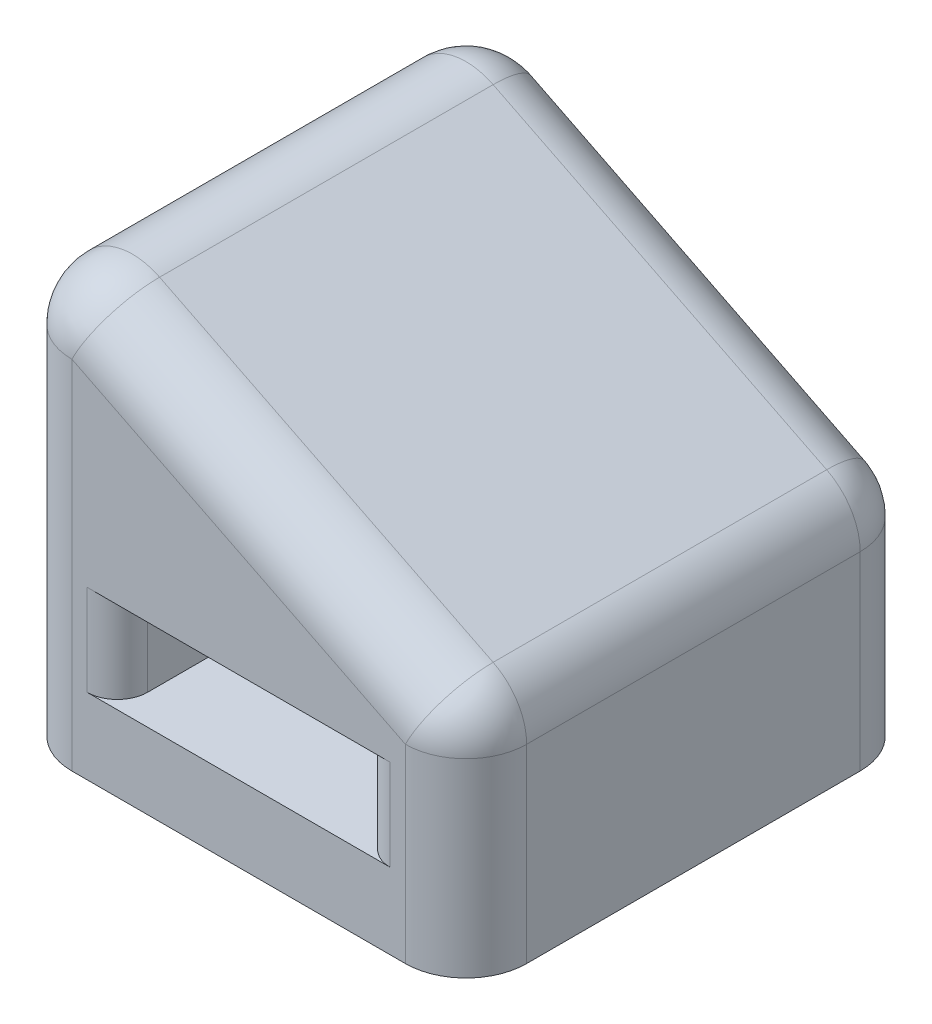
SolidWorks part; units mm, degrees
ref_plane "Plano frontal" through (0, 0, 0) normal (0, 0, 1) x (1, 0, 0)
ref_plane "Plano superior" through (0, 0, 0) normal (0, 1, 0) x (1, 0, 0)
ref_plane "Plano direito" through (0, 0, 0) normal (1, 0, 0) x (0, 0, -1)
sketch "Esboço1" plane through (0, 0, 0) normal (0, 1, 0) x (1, 0, 0)
  line L1 (-5.5, -7.5) -> (5.5, -7.5)
  line L2 (-7.5, -5.5) -> (-7.5, 5.5)
  line L3 (-5.5, 7.5) -> (5.5, 7.5)
  line L4 (7.5, -5.5) -> (7.5, 5.5)
  line L5 (-7.5, -7.5) -> (7.5, 7.5) construction
  line L6 (-7.5, 7.5) -> (7.5, -7.5) construction
  arc A0 (7.5, 5.5) -> (5.5, 7.5) centre (5.5, 5.5) ccw
  arc A1 (7.5, -5.5) -> (5.5, -7.5) centre (5.5, -5.5) cw
  arc A2 (-5.5, -7.5) -> (-7.5, -5.5) centre (-5.5, -5.5) cw
  arc A3 (-7.5, 5.5) -> (-5.5, 7.5) centre (-5.5, 5.5) cw
  point P0 (0, 0)
  dimension "D3" = 2
  dimension "D1" = 15
  dimension "D2" = 15
extrude "Ressalto-extrusão1" add sketch "Esboço1" along normal blind 15
sketch "Esboço2" plane through (0, 0, 7.5) normal (0, 0, 1) x (1, 0, 0)
  line L0 (-7.5, 15) -> (7.5, 7.5)
  line L1 (7.5, 15) -> (7.5, 0) construction
  line L2 (7.5, 7.5) -> (7.5, 15)
  line L3 (7.5, 15) -> (-7.5, 15)
extrude "Corte-extrusão1" cut sketch "Esboço2" against normal blind 15
fillet "Filete1" radius 2 1 edges at (-7.5, 15, 0) type face fillet first side face at (0, 11.25, 0) second side face at (-7.5, 7.5, 0)
sketch "Esboço3" plane through (0, 0, 7.5) normal (0, 0, 1) x (1, 0, 0)
  line L0 (-5.5, 0) -> (5.5, 0) construction
  line L1 (-4, 2.5) -> (4, 2.5)
  line L2 (-4, 2.5) -> (-4, 5.5)
  line L3 (-4, 5.5) -> (4, 5.5)
  line L4 (4, 2.5) -> (4, 5.5)
  line L5 (-4, 2.5) -> (4, 5.5) construction
  line L6 (-4, 5.5) -> (4, 2.5) construction
  point P0 (0, 4)
  point P5 (0, 0)
  dimension "D1" = 8
  dimension "D2" = 0
  dimension "D3" = 4
  dimension "D4" = 3
extrude "Corte-extrusão2" cut sketch "Esboço3" against normal blind 15
fillet "Filete2" radius 1 1 edges at (-4, 4, 7.5) type face fillet first side face at (0, 4, 7.5) second side face at (-4, 4, 0)
fillet "Filete3" radius 1 1 edges at (4, 4, 7.5) type face fillet first side face at (4, 4, 0) second side face at (-0.5, 4, 7.5)
fillet "Filete4" radius 1 1 edges at (-4, 4, -7.5) type face fillet first side face at (-4, 4, -0.5) second side face at (0, 4, -7.5)
fillet "Filete5" radius 1 1 edges at (4, 4, -7.5) type face fillet first side face at (4, 4, -0.5) second side face at (-0.5, 4, -7.5)
